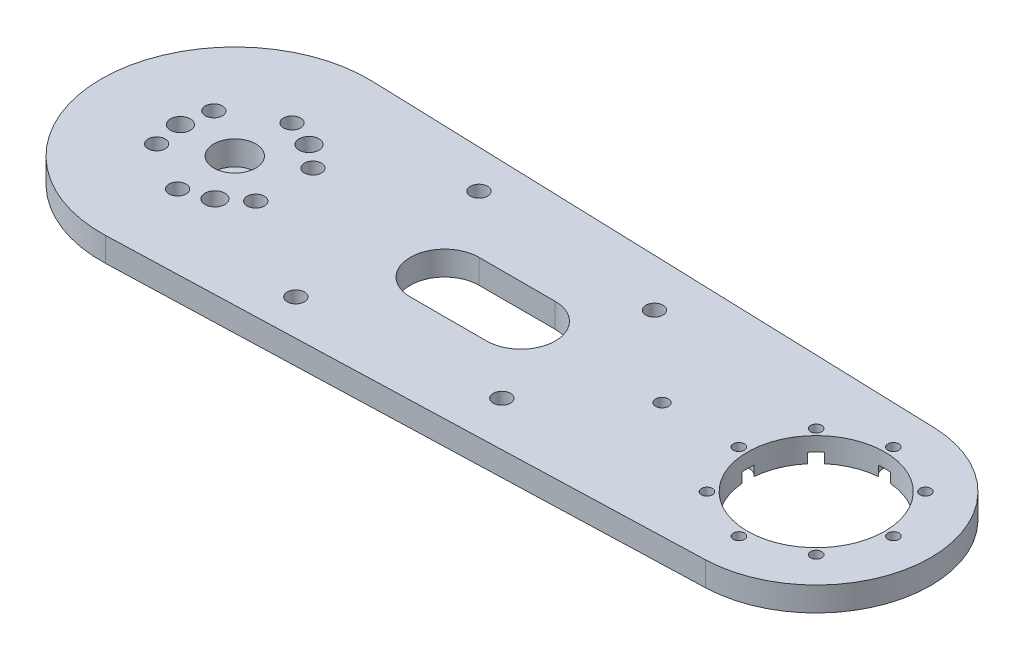
SolidWorks part; units mm, degrees
material "Aleación 6061"
ref_plane "Alzado" through (0, 0, 0) normal (0, 0, 1) x (1, 0, 0)
ref_plane "Planta" through (0, 0, 0) normal (0, 1, 0) x (1, 0, 0)
ref_plane "Vista lateral" through (0, 0, 0) normal (1, 0, 0) x (0, 0, -1)
ref_plane "Plano_zJ2" through (0, 0, 171.45) normal (0, 0, 1) x (1, 0, 0)
ref_plane "Plano_xJ3" through (152.4, 0, 0) normal (1, 0, 0) x (0, 0, -1)
ref_axis "Eje_J2" through (0, -3.4925, 171.45) along (0, 1, 0)
ref_axis "Eje_J3" through (152.4, -3.4925, 171.45) along (0, 1, 0)
sketch "Croquis13" plane through (0, 0, 0) normal (0, 1, 0) x (1, 0, 0)
  line L0 (1.1483, -206.4312) -> (153.3843, -201.4338)
  line L1 (153.3843, -201.4338) -> (153.3843, -141.4662)
  line L2 (153.3843, -141.4662) -> (1.1483, -136.4688)
  line L3 (1.1483, -136.4688) -> (1.1483, -206.4312)
  dimension "D1" = 1.1483
  dimension "D2" = 206.4312
  dimension "D3" = 153.3843
  dimension "D4" = 201.4338
  dimension "D5" = 153.3843
  dimension "D6" = 141.4662
  dimension "D7" = 1.1483
  dimension "D8" = 136.4688
extrude "Placa" add sketch "Croquis13" along normal blind 6.35 from offset 4
sketch "Croquis14" plane through (0, 0, 0) normal (0, 1, 0) x (1, 0, 0)
  circle A0 centre (0, -171.45) radius 35
  dimension "D1" = 70
  dimension "D2" = 171.45
extrude "Placa_r1" add sketch "Croquis14" along normal blind 6.35 from offset 4
sketch "Croquis15" plane through (0, 0, 0) normal (0, 1, 0) x (1, 0, 0)
  circle A0 centre (152.4, -171.45) radius 30
  dimension "D1" = 60
  dimension "D2" = 152.4
  dimension "D3" = 171.45
extrude "Placa_r2" add sketch "Croquis15" along normal blind 6.35 from offset 4
sketch "Croquis16" plane through (0, 0, 0) normal (0, 1, 0) x (1, 0, 0)
  line L0 (55, -162.45) -> (75, -162.45)
  line L1 (75, -180.45) -> (55, -180.45)
  arc A0 (75, -162.45) -> (75, -180.45) centre (75, -171.45) cw
  arc A1 (55, -180.45) -> (55, -162.45) centre (55, -171.45) cw
  dimension "D1" = 9
  dimension "D2" = 9
  dimension "D3" = 55
  dimension "D4" = 162.45
  dimension "D5" = 75
  dimension "D6" = 162.45
  dimension "D7" = 75
  dimension "D8" = 180.45
  dimension "D9" = 55
  dimension "D10" = 180.45
extrude "Aligerado" cut sketch "Croquis16" along normal blind 6.35 from offset 4
sketch "Croquis17" plane through (0, 0, 0) normal (0, 1, 0) x (1, 0, 0)
  circle A0 centre (40, -195.45) radius 2.25
  circle A1 centre (40, -147.45) radius 2.25
  circle A2 centre (90, -191.45) radius 2.25
  circle A3 centre (90, -151.45) radius 2.25
  dimension "D1" = 4.5
  dimension "D2" = 4.5
  dimension "D3" = 4.5
  dimension "D4" = 4.5
  dimension "D5" = 40
  dimension "D6" = 195.45
  dimension "D7" = 40
  dimension "D8" = 147.45
  dimension "D9" = 90
  dimension "D10" = 191.45
  dimension "D11" = 90
  dimension "D12" = 151.45
extrude "Barrenos_separadores_M4" cut sketch "Croquis17" along normal blind 6.35 from offset 4
sketch "Croquis18" plane through (0, 0, 0) normal (0, 1, 0) x (1, 0, 0)
  circle A0 centre (12.9904, -178.95) radius 2.25
  circle A1 centre (0, -186.45) radius 2.25
  circle A2 centre (-12.9904, -178.95) radius 2.25
  circle A3 centre (-12.9904, -163.95) radius 2.25
  circle A4 centre (0, -156.45) radius 2.25
  circle A5 centre (12.9904, -163.95) radius 2.25
  circle A6 centre (7.125, -183.7909) radius 2.6
  circle A7 centre (-14.25, -171.45) radius 2.6
  circle A8 centre (7.125, -159.1091) radius 2.6
  circle A9 centre (0, -171.45) radius 5.5
  circle A10 centre (152.4, -171.45) radius 18
  circle A11 centre (172.65, -171.45) radius 1.45
  circle A12 centre (166.7189, -185.7689) radius 1.45
  circle A13 centre (152.4, -191.7) radius 1.45
  circle A14 centre (138.0811, -185.7689) radius 1.45
  circle A15 centre (132.15, -171.45) radius 1.45
  circle A16 centre (138.0811, -157.1311) radius 1.45
  circle A17 centre (152.4, -151.2) radius 1.45
  circle A18 centre (166.7189, -157.1311) radius 1.45
  dimension "D1" = 4.5
  dimension "D2" = 4.5
  dimension "D3" = 4.5
  dimension "D4" = 4.5
  dimension "D5" = 4.5
  dimension "D6" = 4.5
  dimension "D7" = 5.2
  dimension "D8" = 5.2
  dimension "D9" = 5.2
  dimension "D10" = 11
  dimension "D11" = 36
  dimension "D12" = 2.9
  dimension "D13" = 2.9
  dimension "D14" = 2.9
  dimension "D15" = 2.9
  dimension "D16" = 2.9
  dimension "D17" = 2.9
  dimension "D18" = 2.9
  dimension "D19" = 2.9
  dimension "D20" = 12.9904
  dimension "D21" = 178.95
  dimension "D22" = 186.45
  dimension "D23" = 12.9904
  dimension "D24" = 178.95
  dimension "D25" = 12.9904
  dimension "D26" = 163.95
  dimension "D27" = 156.45
  dimension "D28" = 12.9904
  dimension "D29" = 163.95
  dimension "D30" = 7.125
  dimension "D31" = 183.7909
  dimension "D32" = 14.25
  dimension "D33" = 171.45
  dimension "D34" = 7.125
  dimension "D35" = 159.1091
  dimension "D36" = 171.45
  dimension "D37" = 152.4
  dimension "D38" = 171.45
  dimension "D39" = 172.65
  dimension "D40" = 171.45
  dimension "D41" = 166.7189
  dimension "D42" = 185.7689
  dimension "D43" = 152.4
  dimension "D44" = 191.7
  dimension "D45" = 138.0811
  dimension "D46" = 185.7689
  dimension "D47" = 132.15
  dimension "D48" = 171.45
  dimension "D49" = 138.0811
  dimension "D50" = 157.1311
  dimension "D51" = 152.4
  dimension "D52" = 151.2
  dimension "D53" = 166.7189
  dimension "D54" = 157.1311
extrude "Barrenos_M2_y_M3" cut sketch "Croquis18" along normal blind 6.35 from offset 4
sketch "Croquis19" plane through (0, 0, 0) normal (0, 1, 0) x (1, 0, 0)
  circle A0 centre (12.9904, -178.95) radius 4
  circle A1 centre (0, -186.45) radius 4
  circle A2 centre (-12.9904, -178.95) radius 4
  circle A3 centre (-12.9904, -163.95) radius 4
  circle A4 centre (0, -156.45) radius 4
  circle A5 centre (12.9904, -163.95) radius 4
  dimension "D1" = 8
  dimension "D2" = 8
  dimension "D3" = 8
  dimension "D4" = 8
  dimension "D5" = 8
  dimension "D6" = 8
  dimension "D7" = 12.9904
  dimension "D8" = 178.95
  dimension "D9" = 186.45
  dimension "D10" = 12.9904
  dimension "D11" = 178.95
  dimension "D12" = 12.9904
  dimension "D13" = 163.95
  dimension "D14" = 156.45
  dimension "D15" = 12.9904
  dimension "D16" = 163.95
extrude "Refrentado_M4_cabeza_baja" cut sketch "Croquis19" along normal blind 2.8 from offset 4
sketch "Croquis20" plane through (0, 0, 0) normal (0, 1, 0) x (1, 0, 0)
  circle A0 centre (172.65, -171.45) radius 2.8
  circle A1 centre (166.7189, -185.7689) radius 2.8
  circle A2 centre (152.4, -191.7) radius 2.8
  circle A3 centre (138.0811, -185.7689) radius 2.8
  circle A4 centre (132.15, -171.45) radius 2.8
  circle A5 centre (138.0811, -157.1311) radius 2.8
  circle A6 centre (152.4, -151.2) radius 2.8
  circle A7 centre (166.7189, -157.1311) radius 2.8
  dimension "D1" = 5.6
  dimension "D2" = 5.6
  dimension "D3" = 5.6
  dimension "D4" = 5.6
  dimension "D5" = 5.6
  dimension "D6" = 5.6
  dimension "D7" = 5.6
  dimension "D8" = 5.6
  dimension "D9" = 172.65
  dimension "D10" = 171.45
  dimension "D11" = 166.7189
  dimension "D12" = 185.7689
  dimension "D13" = 152.4
  dimension "D14" = 191.7
  dimension "D15" = 138.0811
  dimension "D16" = 185.7689
  dimension "D17" = 132.15
  dimension "D18" = 171.45
  dimension "D19" = 138.0811
  dimension "D20" = 157.1311
  dimension "D21" = 152.4
  dimension "D22" = 151.2
  dimension "D23" = 166.7189
  dimension "D24" = 157.1311
extrude "Refrentado_M2-5" cut sketch "Croquis20" along normal blind 2.6 from offset 4
sketch "Croquis21" plane through (0, 0, 0) normal (0, 1, 0) x (1, 0, 0)
  circle A0 centre (112, -171.45) radius 1.25
  dimension "D1" = 2.5
  dimension "D2" = 112
  dimension "D3" = 171.45
extrude "Rosca_M3_bases_cincho" cut sketch "Croquis21" along normal blind 6.35 from offset 4
sketch "Croquis22" plane through (0, 0, 0) normal (0, 1, 0) x (1, 0, 0)
  circle A0 centre (112, -171.45) radius 1.7
  dimension "D1" = 3.4
  dimension "D2" = 112
  dimension "D3" = 171.45
extrude "Paso_M3_bases_cincho" cut sketch "Croquis22" along normal blind 6.35 from offset 4
sketch "Croquis23" plane through (0, 4, 0) normal (0, -1, 0) x (1, 0, 0)
  circle A0 centre (0, 171.45) radius 10
  dimension "D1" = 20
extrude "Saliente-Extruir1" add sketch "Croquis23" along normal blind 8
sketch "Croquis24" plane through (0, -4, 0) normal (0, -1, 0) x (1, 0, 0)
  circle A0 centre (0, 171.45) radius 7.475
extrude "Cortar-Extruir1" cut sketch "Croquis24" against normal blind 5.5
